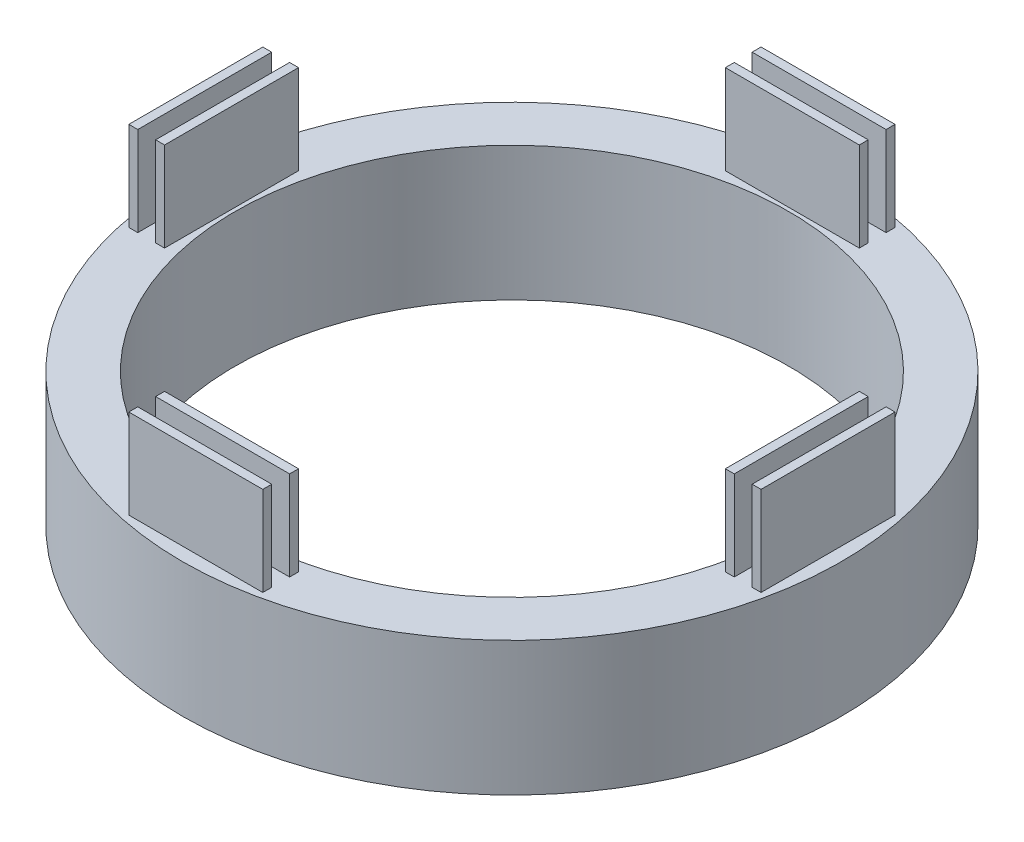
SolidWorks part; units mm, degrees
material "3.0205 (EN-AW 1200)"
ref_plane "Plan de face" through (0, 0, 0) normal (0, 0, 1) x (1, 0, 0)
ref_plane "Plan de dessus" through (0, 0, 0) normal (0, 1, 0) x (1, 0, 0)
ref_plane "Plan de droite" through (0, 0, 0) normal (1, 0, 0) x (0, 0, -1)
sketch "Esquisse1" plane through (0, 0, 0) normal (0, 1, 0) x (1, 0, 0)
  circle A0 centre (0, 0) radius 62
  circle A1 centre (0, 0) radius 73.8
  dimension "D1" = 147.6
  dimension "D2" = 124
extrude "Boss.-Extru.1" add sketch "Esquisse1" along normal blind 30
sketch "Esquisse2" plane through (0, 30, 0) normal (0, 1, 0) x (1, 0, 0)
  line L0 (-109.0313, 0) -> (186.0934, 0) construction
  line L1 (-70.7864, 15) -> (-62.7864, 15)
  line L2 (-70.7864, 15) -> (-70.7864, -15)
  line L3 (-70.7864, -15) -> (-62.7864, -15)
  line L4 (-62.7864, 15) -> (-62.7864, -15)
  line L5 (15, 70.7864) -> (-15, 70.7864)
  line L6 (-68.7864, 15) -> (-64.7864, 15)
  line L7 (-68.7864, 15) -> (-68.7864, -15)
  line L8 (-68.7864, -15) -> (-64.7864, -15)
  line L9 (-64.7864, 15) -> (-64.7864, -15)
  line L10 (15, 68.7864) -> (-15, 68.7864)
  line L11 (15, 64.7864) -> (-15, 64.7864)
  line L12 (15, 62.7864) -> (-15, 62.7864)
  line L13 (-15, 70.7864) -> (-15, 62.7864)
  line L14 (15, 70.7864) -> (15, 62.7864)
  line L15 (70.7864, -15) -> (70.7864, 15)
  line L16 (68.7864, -15) -> (68.7864, 15)
  line L17 (64.7864, -15) -> (64.7864, 15)
  line L18 (62.7864, -15) -> (62.7864, 15)
  line L19 (70.7864, 15) -> (62.7864, 15)
  line L20 (70.7864, -15) -> (62.7864, -15)
  line L21 (-15, -70.7864) -> (15, -70.7864)
  line L22 (-15, -68.7864) -> (15, -68.7864)
  line L23 (-15, -64.7864) -> (15, -64.7864)
  line L24 (-15, -62.7864) -> (15, -62.7864)
  line L25 (15, -70.7864) -> (15, -62.7864)
  line L26 (-15, -70.7864) -> (-15, -62.7864)
  point P38 (0, 0)
  dimension "D1" = 30
  dimension "D2" = 8
  dimension "D3" = 15
  dimension "D4" = 4
  dimension "D5" = 2
  dimension "D6" = 4
extrude "Boss.-Extru.2" add sketch "Esquisse2" along normal blind 20 contours L2 L0 L7 L1 | L0 L2 L3 L7 | L0 L9 L3 L4 | L9 L0 L4 L1 | L14 L5 L13 L10 | L14 L11 L13 L12 | L0 L18 L20 L17 | L18 L0 L17 L19 | L16 L0 L15 L19 | L0 L16 L20 L15 | L26 L21 L25 L22 | L26 L23 L25 L24 region at (-69.7864, 30, -7.5) region at (63.7864, 30, -7.5) region at (63.7864, 30, 7.5) region at (-69.7864, 30, 7.5) region at (-63.7864, 30, -7.5) region at (-63.7864, 30, 7.5) region at (69.7864, 30, -7.5) region at (69.7864, 30, 7.5) region at (0, 30, -69.7864) region at (0, 30, -63.7864) region at (0, 30, 69.7864) region at (0, 30, 63.7864)
